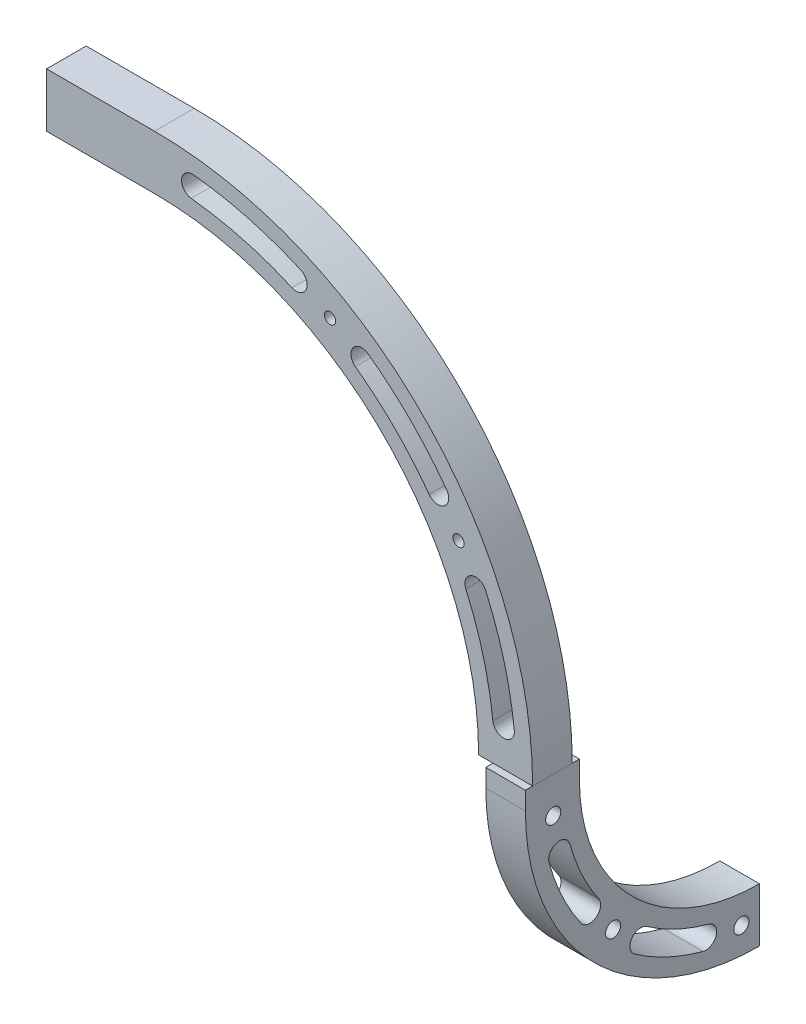
SolidWorks part; units mm, degrees
material "ABS"
ref_plane "前视基准面" through (0, 0, 0) normal (0, 0, 1) x (1, 0, 0)
ref_plane "上视基准面" through (0, 0, 0) normal (0, 1, 0) x (1, 0, 0)
ref_plane "右视基准面" through (0, 0, 0) normal (1, 0, 0) x (0, 0, -1)
other "Configuration Table"
sketch "草图1" plane through (0, 0, 0) normal (0, 0, 1) x (1, 0, 0)
  line L0 (0, 105) -> (0, 0) construction
  line L1 (0, 0) -> (105, 0) construction
  line L2 (90, 0) -> (105, 0)
  line L3 (0, 105) -> (0, 90)
  arc A0 (0, 105) -> (105, 0) centre (0, 0) cw
  arc A1 (0, 90) -> (90, 0) centre (0, 0) cw
  dimension "D1" = 105
  dimension "D2" = 90
extrude "凸台-拉伸1" add sketch "草图1" along normal blind 15
sketch "草图2" plane through (0, 0, 0) normal (0, -1, 0) x (1, 0, 0)
  line L1 (90, 15) -> (105, 15)
  line L2 (90, 15) -> (90, 0)
  line L3 (90, 0) -> (105, 0)
  line L4 (105, 15) -> (105, 0)
extrude "凸台-拉伸2" add sketch "草图2" along normal blind 5
sketch "草图3" plane through (105, 0, 0) normal (1, 0, 0) x (0, 0, -1)
  line L0 (0, -5) -> (50, -5) construction
  line L1 (50, -5) -> (50, -55) construction
  line L2 (50, -55) -> (50, -70)
  line L3 (-15, -5) -> (0, -5)
  arc A0 (0, -5) -> (50, -55) centre (50, -5) ccw
  arc A1 (-15, -5) -> (50, -70) centre (50, -5) ccw
  dimension "D1" = 50
extrude "凸台-拉伸3" add sketch "草图3" against normal blind 15
sketch "草图4" plane through (0, 0, 15) normal (0, 0, 1) x (1, 0, 0)
  line L0 (25.2349, 94.1778) -> (0, 0) construction
  line L1 (0, 0) -> (68.9429, 68.9429) construction
  line L2 (0, 0) -> (94.1778, 25.2349) construction
  line L3 (0, 0) -> (90, 0) construction
  line L4 (48.75, 84.4375) -> (0, 0) construction
  line L5 (84.4375, 48.75) -> (0, 0) construction
  arc A0 (10.4903, 96.934) -> (39.3822, 89.1925) centre (0, 0) cw construction
  arc A1 (40.5939, 91.9368) -> (10.813, 99.9166) centre (0, 0) ccw
  arc A2 (38.1704, 86.4481) -> (10.1675, 93.9514) centre (0, 0) ccw
  arc A3 (38.1704, 86.4481) -> (40.5939, 91.9368) centre (39.3822, 89.1925) ccw
  arc A4 (10.813, 99.9166) -> (10.1675, 93.9514) centre (10.4903, 96.934) ccw
  arc A5 (57.5518, 78.7022) -> (78.7022, 57.5518) centre (0, 0) cw construction
  arc A6 (81.1238, 59.3227) -> (59.3227, 81.1238) centre (0, 0) ccw
  arc A7 (76.2806, 55.781) -> (55.781, 76.2806) centre (0, 0) ccw
  arc A8 (76.2806, 55.781) -> (81.1238, 59.3227) centre (78.7022, 57.5518) ccw
  arc A9 (59.3227, 81.1238) -> (55.781, 76.2806) centre (57.5518, 78.7022) ccw
  arc A10 (89.1925, 39.3822) -> (96.934, 10.4903) centre (0, 0) cw construction
  arc A11 (99.9166, 10.813) -> (91.9368, 40.5939) centre (0, 0) ccw
  arc A12 (93.9514, 10.1675) -> (86.4481, 38.1704) centre (0, 0) ccw
  arc A13 (93.9514, 10.1675) -> (99.9166, 10.813) centre (96.934, 10.4903) ccw
  arc A14 (91.9368, 40.5939) -> (86.4481, 38.1704) centre (89.1925, 39.3822) ccw
  circle A17 centre (84.4375, 48.75) radius 1.55
  circle A18 centre (48.75, 84.4375) radius 1.55
  point P4 (25.2349, 94.1778)
  point P9 (68.9429, 68.9429)
  point P18 (94.1778, 25.2349)
  dimension "D1" = 3
  dimension "D2" = 3
  dimension "D3" = 3
  dimension "D7" = 97.5
  dimension "D8" = 97.5
  dimension "D9" = 97.5
  dimension "D12" = 3.1
  dimension "D13" = 3.1
  dimension "D14" = 15
  dimension "D4" = 15
  dimension "D5" = 45
  dimension "D6" = 75
  dimension "D10" = 97.5
  dimension "D11" = 97.5
  dimension "D15" = 15
  dimension "D16" = 15
  dimension "D17" = 15
  dimension "D18" = 15
sketch "草图5" plane through (105, 0, 0) normal (1, 0, 0) x (0, 0, -1)
  line L0 (-2.1127, -29.3006) -> (50, -5) construction
  line L1 (50, -5) -> (25.6994, -57.1127) construction
  line L2 (50, -55) -> (50, -5) construction
  line L3 (50, -5) -> (0, -5) construction
  line L4 (-7.2812, -10.0115) -> (50, -5) construction
  line L5 (50, -5) -> (9.3414, -45.6586) construction
  line L6 (50, -5) -> (44.9694, -62.5) construction
  arc A0 (-5.5348, -19.9043) -> (2.8856, -37.9618) centre (50, -5) ccw construction
  arc A1 (-8.4322, -20.6819) -> (0.4274, -39.6816) centre (50, -5) ccw
  arc A2 (-2.6373, -19.1267) -> (5.3437, -36.2421) centre (50, -5) ccw
  arc A3 (-2.6373, -19.1267) -> (-8.4322, -20.6819) centre (-5.5348, -19.9043) ccw
  arc A4 (0.4274, -39.6816) -> (5.3437, -36.2421) centre (2.8856, -37.9618) ccw
  arc A5 (17.0382, -52.1144) -> (35.0957, -60.5348) centre (50, -5) ccw construction
  arc A6 (15.3184, -54.5726) -> (34.3181, -63.4322) centre (50, -5) ccw
  arc A7 (18.7579, -49.6563) -> (35.8733, -57.6373) centre (50, -5) ccw
  arc A8 (18.7579, -49.6563) -> (15.3184, -54.5726) centre (17.0382, -52.1144) ccw
  arc A9 (34.3181, -63.4322) -> (35.8733, -57.6373) centre (35.0957, -60.5348) ccw
  circle A13 centre (44.9694, -62.5) radius 1.55
  circle A14 centre (9.3414, -45.6586) radius 1.55
  circle A15 centre (-7.2812, -10.0115) radius 1.55
  point P4 (-2.1127, -29.3006)
  point P9 (25.6994, -57.1127)
  dimension "D1" = 57.5
  dimension "D2" = 57.5
  dimension "D8" = 3.1
  dimension "D9" = 3.1
  dimension "D10" = 3.1
  dimension "D12" = 25
  dimension "D13" = 3
  dimension "D16" = 3
  dimension "D3" = 57.5
  dimension "D4" = 57.5
  dimension "D5" = 57.5
  dimension "D6" = 10
  dimension "D7" = 10
  dimension "D11" = 45
  dimension "D14" = 5
  dimension "D15" = 5
  dimension "D17" = 25
extrude "切除-拉伸1" cut sketch "草图4" against normal through all
extrude "切除-拉伸2" cut sketch "草图5" against normal through all
sketch "草图6" plane through (105, 0, 0) normal (1, 0, 0) x (0, 0, -1)
  line L0 (50, -55) -> (50, -70)
  line L1 (0, -5) -> (-15, -5)
  arc A0 (0, -5) -> (50, -55) centre (50, -5) ccw
  arc A1 (-15, -5) -> (50, -70) centre (50, -5) ccw
extrude "切除-拉伸3" [suppressed] cut sketch "草图6" against normal blind 2
sketch "草图7" plane through (0, 0, 15) normal (0, 0, 1) x (1, 0, 0)
  line L0 (0, 105) -> (0, 90)
  line L1 (90, 0) -> (105, 0)
  line L2 (90, -5) -> (90, 0) construction
  arc A0 (0, 90) -> (90, 0) centre (0, 0) cw
  arc A1 (0, 105) -> (105, 0) centre (0, 0) cw
extrude "切除-拉伸4" cut sketch "草图7" against normal blind 2
sketch "草图8" plane through (90, 0, 0) normal (-1, 0, 0) x (0, 0, 1)
  line L0 (-50, -55) -> (-50, -70)
  line L1 (0, -5) -> (15, -5)
  arc A0 (-50, -55) -> (0, -5) centre (-50, -5) ccw
  arc A1 (-50, -55) -> (0, -5) centre (-50, -5) ccw construction
  arc A2 (-50, -70) -> (15, -5) centre (-50, -5) ccw
extrude "切除-拉伸5" cut sketch "草图8" against normal blind 4
sketch "草图10" plane through (0, 0, 0) normal (0, 0, 1) x (1, 0, 0)
  line L0 (0, 105) -> (0, 90)
  line L1 (90, 0) -> (105, 0)
  arc A0 (0, 90) -> (90, 0) centre (0, 0) cw
  arc A1 (0, 105) -> (105, 0) centre (0, 0) cw
extrude "切除-拉伸6" cut sketch "草图10" along normal blind 2
sketch "草图9" plane through (0, 0, 0) normal (-1, 0, 0) x (0, 0, 1)
  line L0 (13, 105) -> (2, 105) construction
  line L5 (2, 105) -> (13, 105)
  line L6 (2, 105) -> (2, 90)
  line L7 (2, 90) -> (13, 90)
  line L8 (13, 105) -> (13, 90)
  line L9 (13, 90) -> (2, 90) construction
  line L12 (13, 105) -> (2, 105) construction
  point P10 (13, 105)
  point P11 (2, 105)
  point P15 (2, 90)
extrude "凸台-拉伸4" add sketch "草图9" along normal blind 30
sketch "草图11" plane through (90, 0, 0) normal (-1, 0, 0) x (0, 0, 1)
  line L1 (0, 0) -> (15, 0)
  line L2 (0, 0) -> (0, -5)
  line L3 (0, -5) -> (15, -5)
  line L4 (15, 0) -> (15, -5)
extrude "切除-拉伸7" cut sketch "草图11" against normal up to surface (4 mm away) up to face at (94, -62.5, -43.4194)
sketch "草图12" plane through (105, 0, 0) normal (1, 0, 0) x (0, 0, -1)
  circle A0 centre (-7.2812, -10.0115) radius 2.1
  circle A1 centre (9.3414, -45.6586) radius 2.1
  circle A2 centre (44.9694, -62.5) radius 2.1
  dimension "D1" = 4.2
  dimension "D2" = 4.2
  dimension "D3" = 4.2
extrude "切除-拉伸8" cut sketch "草图12" against normal blind 4.5
